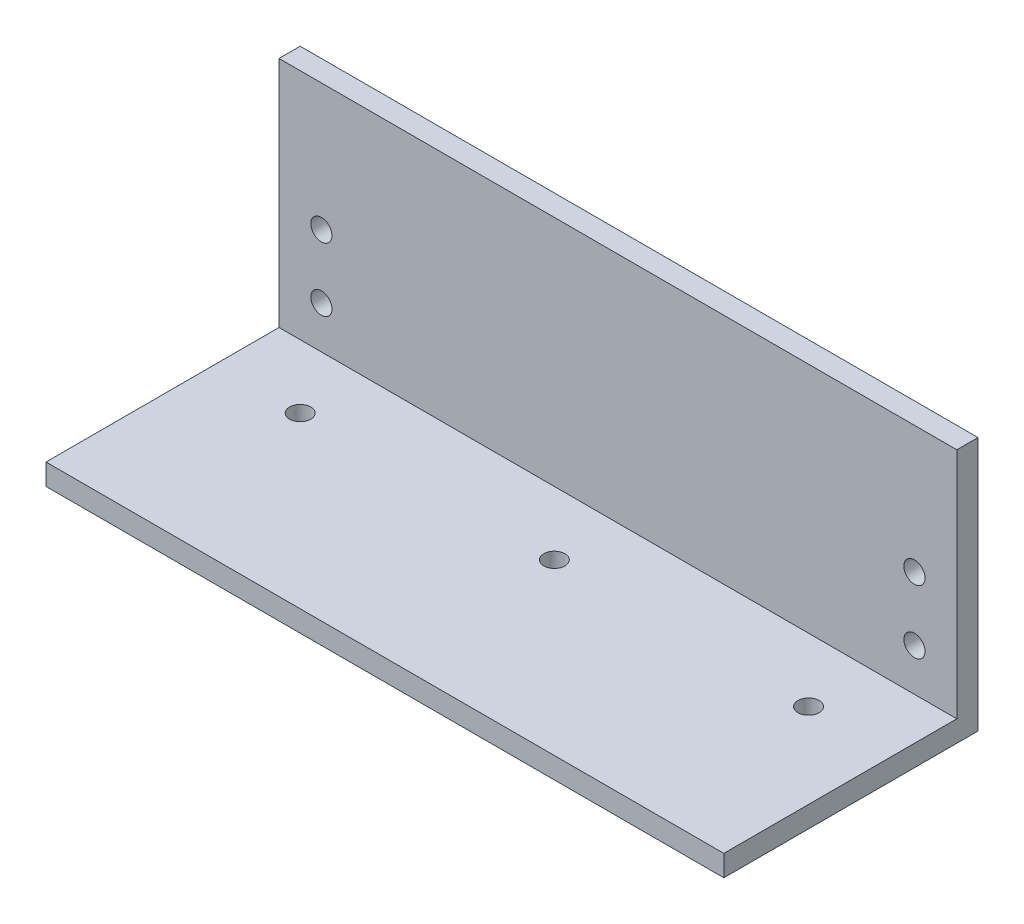
SolidWorks part; units mm, degrees
material "6061 Alloy"
ref_plane "Front Plane" through (0, 0, 0) normal (0, 0, 1) x (1, 0, 0)
ref_plane "Top Plane" through (0, 0, 0) normal (0, 1, 0) x (1, 0, 0)
ref_plane "Right Plane" through (0, 0, 0) normal (1, 0, 0) x (0, 0, -1)
sketch "Sketch2" plane through (0, 0, 0) normal (1, 0, 0) x (0, 0, -1)
  line L1 (0, 0) -> (76.2, 0)
  line L2 (0, 0) -> (0, 76.2)
  line L3 (0, 76.2) -> (76.2, 76.2)
  line L4 (76.2, 0) -> (76.2, 76.2)
  line L5 (0, 76.2) -> (69.85, 76.2)
  line L6 (0, 76.2) -> (0, 6.35)
  line L7 (0, 6.35) -> (69.85, 6.35)
  line L8 (69.85, 76.2) -> (69.85, 6.35)
  dimension "D1" = 76.2
  dimension "D2" = 76.2
  dimension "D3" = 6.35
  dimension "D4" = 6.35
extrude "Boss-Extrude2" add sketch "Sketch2" along normal blind 203.2 contours L3 L8 L7 L2 L1 L4 region at (0, 3.175, -1.0776)
sketch "Sketch4" plane through (0, 0, -76.2) normal (0, 0, -1) x (-1, 0, 0)
  line L0 (-203.2, 0) -> (0, 0) construction
  line L1 (-203.2, 0) -> (-203.2, 76.2) construction
  circle A0 centre (-190.5, 19.05) radius 3.175
  circle A1 centre (-190.5, 38.1) radius 3.175
  circle A2 centre (-12.7, 19.05) radius 3.175
  circle A3 centre (-12.7, 38.1) radius 3.175
  dimension "D1" = 19.05
  dimension "D2" = 12.7
  dimension "D3" = 38.1
  dimension "D4" = 190.5
  dimension "D5" = 38.1
  dimension "D6" = 190.5
extrude "Cut-Extrude1" cut sketch "Sketch4" against normal blind 71.628
sketch "Sketch5" plane through (0, 6.35, 0) normal (0, 1, 0) x (1, 0, 0)
  line L0 (0, 0) -> (0, 69.85) construction
  line L1 (203.2, 0) -> (0, 0) construction
  circle A0 centre (25.4, 50.8) radius 3.175
  circle A1 centre (177.8, 50.8) radius 3.175
  circle A2 centre (101.6, 50.8) radius 3.175
  dimension "D1" = 177.8
  dimension "D2" = 6.35
  dimension "D3" = 50.8
  dimension "D4" = 101.6
  dimension "D5" = 50.8
  dimension "D6" = 50.8
  dimension "D7" = 25.4
extrude "Cut-Extrude2" cut sketch "Sketch5" against normal blind 244.602
